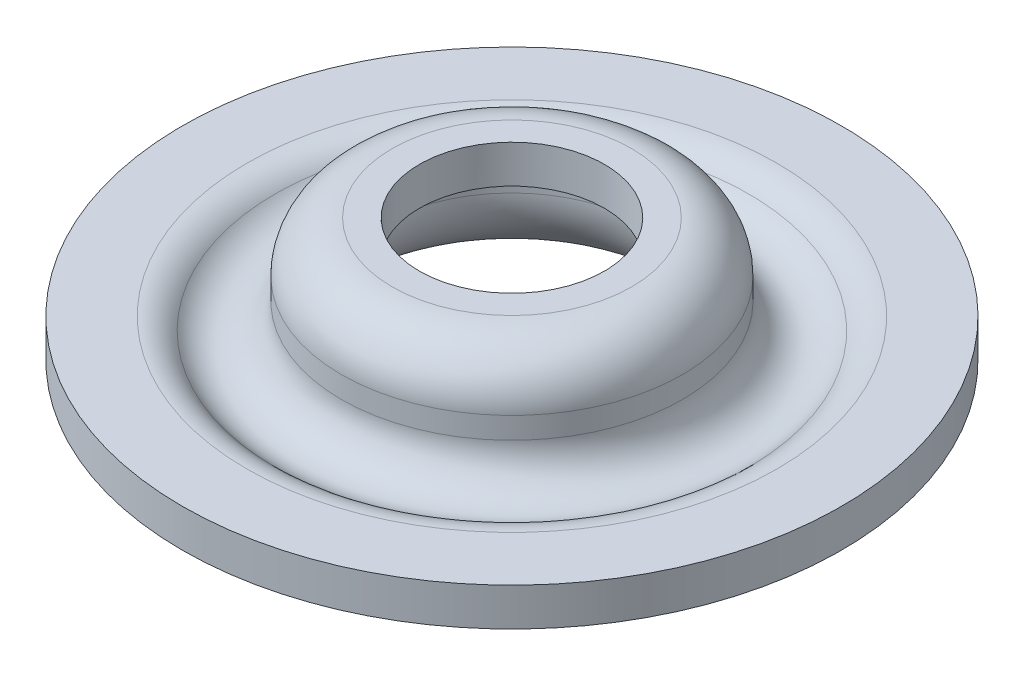
SolidWorks part; units mm, degrees
ref_plane "Front Plane" through (0, 0, 0) normal (0, 0, 1) x (1, 0, 0)
ref_plane "Top Plane" through (0, 0, 0) normal (0, 1, 0) x (1, 0, 0)
ref_plane "Right Plane" through (0, 0, 0) normal (1, 0, 0) x (0, 0, -1)
ref_axis "Axis_X" through (-88.99, 0, 0) along (1, 0, 0)
ref_axis "Axis_Y" through (0, 55, 0) along (0, -1, 0)
ref_axis "Axis_Z" through (0, 0, -88.99) along (0, 0, 1)
sketch "Sketch1" plane through (0, 0, 0) normal (0, 0, 1) x (1, 0, 0)
  line L0 (0, 0) -> (0, 11.698) construction
  line L1 (-26, 4.978) -> (-19.2706, 4.978)
  line L2 (-13.45, 6) -> (-13.45, 7.698)
  line L3 (-9.45, 11.698) -> (0, 11.698)
  line L4 (-26, 4.978) -> (-26, 1.978)
  line L5 (-26, 1.978) -> (-20.9024, 1.978)
  line L6 (-9.45, 8.698) -> (0, 8.698) construction
  line L7 (-10.45, 6) -> (-10.45, 7.698)
  line L8 (-9.45, 8.698) -> (0, 8.698)
  line L9 (-26, 4.978) -> (-26, 4.9152) construction
  line L10 (-25.3895, 1.978) -> (-20.9024, 1.978) construction
  line L11 (-25.3895, 1.978) -> (-25.3895, 1.978) construction
  line L12 (0, 11.698) -> (0, 8.698)
  arc A0 (-19.2706, 4.978) -> (-13.45, 6) centre (-16.45, 6) ccw
  arc A1 (-9.45, 11.698) -> (-13.45, 7.698) centre (-9.45, 7.698) ccw
  arc A2 (-20.9024, 1.978) -> (-10.45, 6) centre (-16.45, 6) ccw
  arc A3 (-9.45, 8.698) -> (-10.45, 7.698) centre (-9.45, 7.698) ccw
  dimension "FIX_1" = 6
  dimension "FIX_4" = 8
  dimension "FIX_2" = 32.9
  dimension "FIX_3" = 6
  dimension "FIX_5" = 11.698
  dimension "FIX_6" = 6.72
  dimension "FIX_7" = 52
  dimension "FIX_8" = 3
revolve "Revolve1" add sketch "Sketch1" angle 360 about axis through (0, 55, 0) along (0, -1, 0)
fillet "Fillet1" radius 3 1 edges at (0, 4.978, 19.2706)
sketch "Sketch2" plane through (0, 11.698, 0) normal (0, 1, 0) x (1, 0, 0)
  circle A0 centre (0, 0) radius 7.3
  dimension "FIX_11" = 14.6
extrude "Cut-Extrude1" cut sketch "Sketch2" against normal through all
equation "\"Factor\"= 1.082532"
